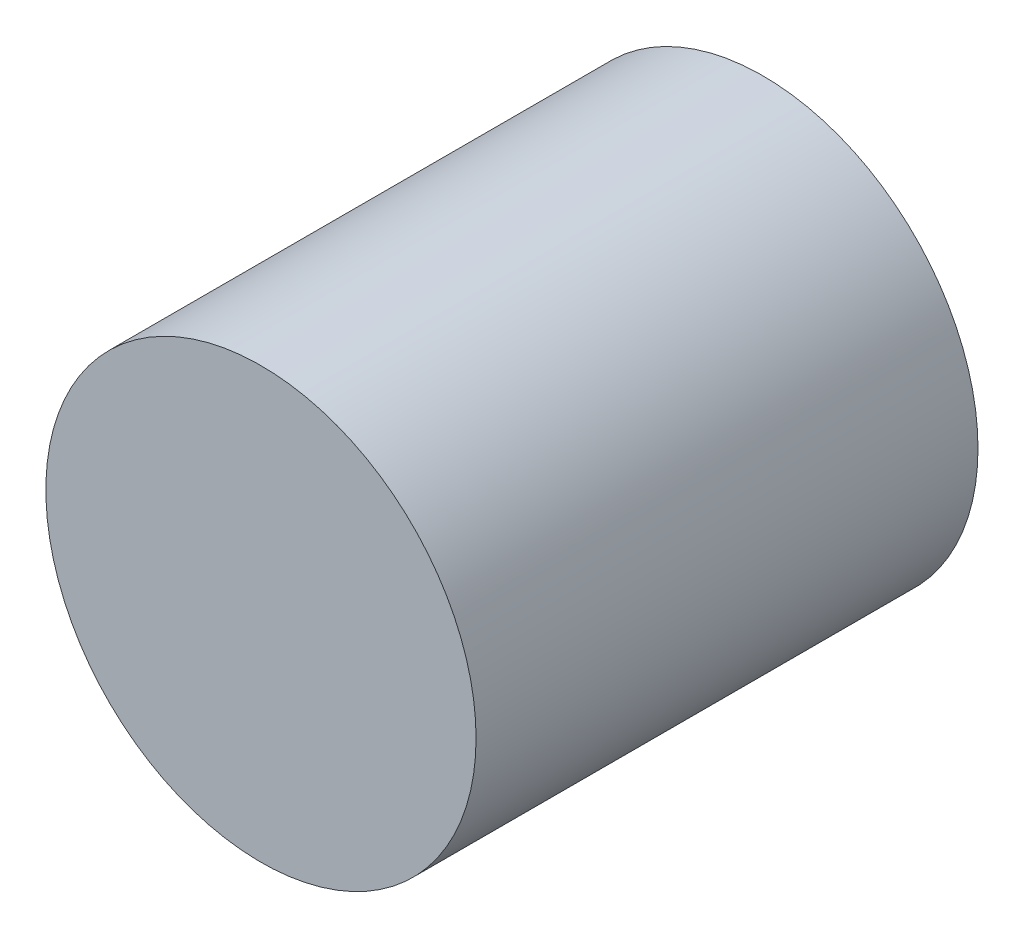
SolidWorks part; units mm, degrees
ref_plane "Спереди" through (0, 0, 0) normal (0, 0, 1) x (1, 0, 0)
ref_plane "Сверху" through (0, 0, 0) normal (0, 1, 0) x (1, 0, 0)
ref_plane "Справа" through (0, 0, 0) normal (1, 0, 0) x (0, 0, -1)
other "Configuration Table"
sketch "Эскиз1" plane through (0, 0, 0) normal (0, 0, 1) x (1, 0, 0)
  circle A0 centre (0, 0) radius 30
  dimension "D1" = 60
extrude "Бобышка-Вытянуть1" add sketch "Эскиз1" along normal blind 70
